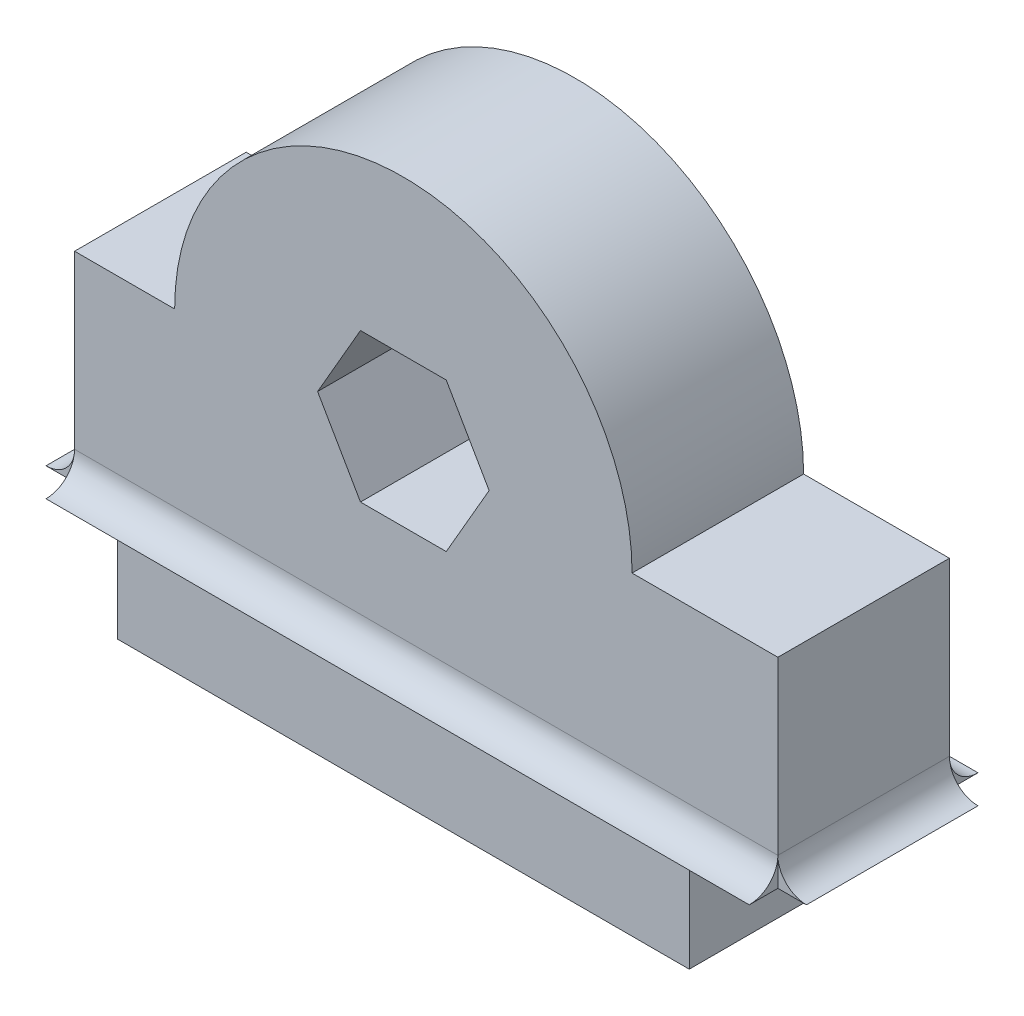
SolidWorks part; units mm, degrees
ref_plane "Front Plane" through (0, 0, 0) normal (0, 0, 1) x (1, 0, 0)
ref_plane "Top Plane" through (0, 0, 0) normal (0, 1, 0) x (1, 0, 0)
ref_plane "Right Plane" through (0, 0, 0) normal (1, 0, 0) x (0, 0, -1)
sketch "Sketch1" plane through (0, 0, 0) normal (0, 0, 1) x (1, 0, 0)
  line L0 (0, 0) -> (20, 0)
  line L1 (0, 0) -> (0, 4)
  line L2 (20, 0) -> (20, 4)
  line L3 (0, 4) -> (-1.5, 4)
  line L4 (23.1, 11) -> (23.1, 4)
  line L5 (-1.5, 4) -> (-1.5, 11)
  line L6 (-1.5, 11) -> (2, 11)
  line L7 (18, 11) -> (23.1, 11)
  line L8 (23.1, 4) -> (20, 4)
  line L11 (13, 11) -> (11.5, 13.5981)
  line L12 (11.5, 13.5981) -> (8.5, 13.5981)
  line L13 (8.5, 13.5981) -> (7, 11)
  line L14 (7, 11) -> (8.5, 8.4019)
  line L15 (8.5, 8.4019) -> (11.5, 8.4019)
  line L16 (11.5, 8.4019) -> (13, 11)
  arc A0 (18, 11) -> (2, 11) centre (10, 11) ccw
  dimension "D1" = 8
  dimension "D5" = 11.5
  dimension "D6" = 20
  dimension "D2" = 7
  dimension "D3" = 8.5
  dimension "D4" = 10
  dimension "D7" = 23.1
  dimension "D8" = 1.5
  dimension "D9" = 4
  dimension "D10" = 8.4019
extrude "Boss-Extrude1" add sketch "Sketch1" along normal blind 6
sketch "Sketch2" plane through (-1.5, 0, 0) normal (-1, 0, 0) x (0, 0, 1)
  line L0 (3, 0) -> (3, 7) construction
  line L1 (6, 4) -> (6, 5)
  line L2 (6, 4) -> (7, 4)
  line L3 (0, 4) -> (-1, 4)
  line L4 (0, 4) -> (0, 5)
  arc A0 (6, 5) -> (7, 4) centre (7, 5) ccw
  arc A1 (0, 5) -> (-1, 4) centre (-1, 5) cw
  dimension "D1" = 1
  dimension "D2" = 1
  dimension "D3" = 6
  dimension "D4" = 3
  dimension "D5" = 4
extrude "Boss-Extrude2" add sketch "Sketch2" against normal up to surface (24.6 mm away) up to face at (23.1, 7.5, 3)
sketch "Sketch4" plane through (0, 0, 6) normal (0, 0, 1) x (1, 0, 0)
  line L0 (10.8, 0) -> (10.8, 7) construction
  line L1 (23.1, 4) -> (23.1, 5)
  line L2 (23.1, 4) -> (24.1, 4)
  line L3 (-1.5, 4) -> (-2.5, 4)
  line L4 (-1.5, 4) -> (-1.5, 5)
  arc A0 (23.1, 5) -> (24.1, 4) centre (24.1, 5) ccw
  arc A1 (-1.5, 5) -> (-2.5, 4) centre (-2.5, 5) cw
  dimension "D1" = 1
  dimension "D2" = 1
  dimension "D3" = 10.8
  dimension "D4" = 12.3
  dimension "D5" = 4
extrude "Boss-Extrude3" add sketch "Sketch4" against normal up to surface (6 mm away) up to face at (10, 11, 0)
